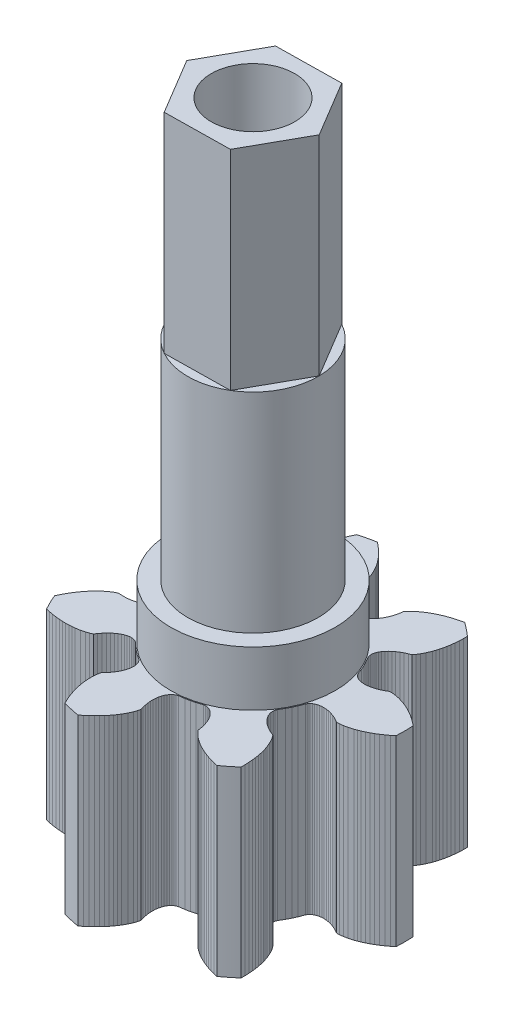
SolidWorks part; units mm, degrees
ref_plane "Front Plane" through (0, 0, 0) normal (0, 0, 1) x (1, 0, 0)
ref_plane "Top Plane" through (0, 0, 0) normal (0, 1, 0) x (1, 0, 0)
ref_plane "Right Plane" through (0, 0, 0) normal (1, 0, 0) x (0, 0, -1)
sketch "Sketch1" plane through (0, 0, 0) normal (0, 1, 0) x (1, 0, 0)
  circle A0 centre (0, 0) radius 3.15
  dimension "D1" = 6.3
extrude "Boss-Extrude1" add sketch "Sketch1" along normal blind 2.1
sketch "Sketch2" plane through (0, 2.1, 0) normal (0, 1, 0) x (1, 0, 0)
  circle A0 centre (0, 0) radius 2.5
  dimension "D1" = 5
extrude "Boss-Extrude3" add sketch "Sketch2" along normal blind 16
sketch "Sketch4" plane through (0, 0, 0) normal (0, -1, 0) x (1, 0, 0)
  line L420 (-1.6777, -5.4575) -> (-1.7402, -5.3144)
  line L421 (-1.7402, -5.3144) -> (-1.7939, -5.1757)
  line L422 (-1.7939, -5.1757) -> (-1.8392, -5.0423)
  line L423 (-1.8392, -5.0423) -> (-1.8764, -4.916)
  line L424 (-1.8764, -4.916) -> (-1.9071, -4.7932)
  line L425 (-1.9071, -4.7932) -> (-1.9311, -4.676)
  line L426 (-1.9311, -4.676) -> (-1.9488, -4.5668)
  line L427 (-1.9488, -4.5668) -> (-1.961, -4.464)
  line L428 (-1.961, -4.464) -> (-1.9715, -4.2798)
  line L429 (-1.9715, -4.2798) -> (-1.9674, -4.1246)
  line L430 (-1.9674, -4.1246) -> (-1.9537, -4.0009)
  line L431 (-1.9537, -4.0009) -> (-1.9303, -3.8867)
  line L432 (-1.9303, -3.8867) -> (-1.8594, -3.8097)
  line L433 (-1.8594, -3.8097) -> (-1.7784, -3.7125)
  line L434 (-1.7784, -3.7125) -> (-1.7087, -3.6155)
  line L435 (-1.7087, -3.6155) -> (-1.6501, -3.5195)
  line L436 (-1.6501, -3.5195) -> (-1.6023, -3.4251)
  line L437 (-1.6023, -3.4251) -> (-1.5652, -3.3333)
  line L438 (-1.5652, -3.3333) -> (-1.5384, -3.2446)
  line L439 (-1.5384, -3.2446) -> (-1.5215, -3.1597)
  line L440 (-1.5215, -3.1597) -> (-1.5143, -3.0795)
  line L441 (-1.5143, -3.0795) -> (-1.5162, -3.0043)
  line L442 (-1.5162, -3.0043) -> (-1.5269, -2.935)
  line L443 (-1.5269, -2.935) -> (-1.5457, -2.8721)
  line L444 (-1.5457, -2.8721) -> (-1.5723, -2.8162)
  line L445 (-1.5723, -2.8162) -> (-1.606, -2.7677)
  line L446 (-1.606, -2.7677) -> (-1.6572, -2.7183)
  line L447 (-1.6572, -2.7183) -> (-1.8447, -2.5928)
  line L448 (-1.8447, -2.5928) -> (-1.984, -2.4878)
  line L449 (-1.984, -2.4878) -> (-2.1173, -2.3754)
  line L450 (-2.1173, -2.3754) -> (-2.2814, -2.2205)
  line L451 (-2.2814, -2.2205) -> (-2.341, -2.1815)
  line L452 (-2.341, -2.1815) -> (-2.3957, -2.1595)
  line L453 (-2.3957, -2.1595) -> (-2.4562, -2.146)
  line L454 (-2.4562, -2.146) -> (-2.5217, -2.1417)
  line L455 (-2.5217, -2.1417) -> (-2.5917, -2.1467)
  line L456 (-2.5917, -2.1467) -> (-2.6653, -2.1615)
  line L457 (-2.6653, -2.1615) -> (-2.742, -2.1865)
  line L458 (-2.742, -2.1865) -> (-2.8209, -2.2218)
  line L459 (-2.8209, -2.2218) -> (-2.9014, -2.2676)
  line L460 (-2.9014, -2.2676) -> (-2.9827, -2.3243)
  line L461 (-2.9827, -2.3243) -> (-3.0641, -2.3918)
  line L462 (-3.0641, -2.3918) -> (-3.1447, -2.4703)
  line L463 (-3.1447, -2.4703) -> (-3.2237, -2.5599)
  line L464 (-3.2237, -2.5599) -> (-3.3005, -2.6605)
  line L465 (-3.3005, -2.6605) -> (-3.3598, -2.7467)
  line L466 (-3.3598, -2.7467) -> (-3.4659, -2.795)
  line L467 (-3.4659, -2.795) -> (-3.5835, -2.8358)
  line L468 (-3.5835, -2.8358) -> (-3.7338, -2.8744)
  line L469 (-3.7338, -2.8744) -> (-3.9158, -2.9052)
  line L470 (-3.9158, -2.9052) -> (-4.0187, -2.9161)
  line L471 (-4.0187, -2.9161) -> (-4.1291, -2.9232)
  line L472 (-4.1291, -2.9232) -> (-4.2487, -2.9258)
  line L473 (-4.2487, -2.9258) -> (-4.3752, -2.9233)
  line L474 (-4.3752, -2.9233) -> (-4.5067, -2.9151)
  line L475 (-4.5067, -2.9151) -> (-4.6468, -2.9006)
  line L476 (-4.6468, -2.9006) -> (-4.794, -2.8791)
  line L477 (-4.794, -2.8791) -> (-4.9474, -2.85)
  line L478 (-4.9474, -2.85) -> (-5.0902, -2.8167)
  line L479 (-5.3759, -2.2235) -> (-5.3129, -2.0911)
  line L480 (-5.3129, -2.0911) -> (-5.2399, -1.953)
  line L481 (-5.2399, -1.953) -> (-5.165, -1.8245)
  line L482 (-5.165, -1.8245) -> (-5.089, -1.7059)
  line L483 (-5.089, -1.7059) -> (-5.0134, -1.5981)
  line L484 (-5.0134, -1.5981) -> (-4.9365, -1.4976)
  line L485 (-4.9365, -1.4976) -> (-4.8599, -1.4057)
  line L486 (-4.8599, -1.4057) -> (-4.7855, -1.3238)
  line L487 (-4.7855, -1.3238) -> (-4.7128, -1.2502)
  line L488 (-4.7128, -1.2502) -> (-4.5753, -1.1271)
  line L489 (-4.5753, -1.1271) -> (-4.4514, -1.0336)
  line L490 (-4.4514, -1.0336) -> (-4.3462, -0.9671)
  line L491 (-4.3462, -0.9671) -> (-4.2422, -0.9142)
  line L492 (-4.2422, -0.9142) -> (-4.1379, -0.9217)
  line L493 (-4.1379, -0.9217) -> (-4.0114, -0.9244)
  line L494 (-4.0114, -0.9244) -> (-3.8921, -0.9184)
  line L495 (-3.8921, -0.9184) -> (-3.7804, -0.9043)
  line L496 (-3.7804, -0.9043) -> (-3.6769, -0.8828)
  line L497 (-3.6769, -0.8828) -> (-3.5819, -0.8546)
  line L498 (-3.5819, -0.8546) -> (-3.4959, -0.8203)
  line L499 (-3.4959, -0.8203) -> (-3.4191, -0.7805)
  line L500 (-3.4191, -0.7805) -> (-3.3518, -0.7361)
  line L501 (-3.3518, -0.7361) -> (-3.2942, -0.6878)
  line L502 (-3.2942, -0.6878) -> (-3.2467, -0.6363)
  line L503 (-3.2467, -0.6363) -> (-3.2093, -0.5823)
  line L504 (-3.2093, -0.5823) -> (-3.1821, -0.5267)
  line L505 (-3.1821, -0.5267) -> (-3.1652, -0.4701)
  line L506 (-3.1652, -0.4701) -> (-3.1585, -0.3992)
  line L507 (-3.1585, -0.3992) -> (-3.1773, -0.1744)
  line L508 (-3.1773, -0.1744) -> (-3.1821, 0)
  line L509 (-3.1821, 0) -> (-3.1773, 0.1743)
  line L510 (-3.1773, 0.1743) -> (-3.1585, 0.3991)
  line L511 (-3.1585, 0.3991) -> (-3.1652, 0.47)
  line L512 (-3.1652, 0.47) -> (-3.1821, 0.5266)
  line L513 (-3.1821, 0.5266) -> (-3.2093, 0.5822)
  line L514 (-3.2093, 0.5822) -> (-3.2467, 0.6362)
  line L515 (-3.2467, 0.6362) -> (-3.2942, 0.6877)
  line L516 (-3.2942, 0.6877) -> (-3.3518, 0.7361)
  line L517 (-3.3518, 0.7361) -> (-3.4191, 0.7805)
  line L518 (-3.4191, 0.7805) -> (-3.4959, 0.8202)
  line L519 (-3.4959, 0.8202) -> (-3.5819, 0.8545)
  line L520 (-3.5819, 0.8545) -> (-3.6769, 0.8828)
  line L521 (-3.6769, 0.8828) -> (-3.7804, 0.9043)
  line L522 (-3.7804, 0.9043) -> (-3.8921, 0.9183)
  line L523 (-3.8921, 0.9183) -> (-4.0114, 0.9243)
  line L524 (-4.0114, 0.9243) -> (-4.1379, 0.9216)
  line L525 (-4.1379, 0.9216) -> (-4.2422, 0.9142)
  line L526 (-4.2422, 0.9142) -> (-4.3462, 0.967)
  line L527 (-4.3462, 0.967) -> (-4.4514, 1.0335)
  line L528 (-4.4514, 1.0335) -> (-4.5753, 1.127)
  line L529 (-4.5753, 1.127) -> (-4.7128, 1.2501)
  line L530 (-4.7128, 1.2501) -> (-4.7855, 1.3238)
  line L531 (-4.7855, 1.3238) -> (-4.8599, 1.4056)
  line L532 (-4.8599, 1.4056) -> (-4.9365, 1.4975)
  line L533 (-4.9365, 1.4975) -> (-5.0134, 1.598)
  line L534 (-5.0134, 1.598) -> (-5.089, 1.7059)
  line L535 (-5.089, 1.7059) -> (-5.165, 1.8244)
  line L536 (-5.165, 1.8244) -> (-5.2399, 1.9529)
  line L537 (-5.2399, 1.9529) -> (-5.3129, 2.0911)
  line L538 (-5.3129, 2.0911) -> (-5.3759, 2.2234)
  line L539 (-5.0902, 2.8167) -> (-4.9474, 2.8499)
  line L540 (-4.9474, 2.8499) -> (-4.794, 2.879)
  line L541 (-4.794, 2.879) -> (-4.6468, 2.9005)
  line L542 (-4.6468, 2.9005) -> (-4.5067, 2.9151)
  line L543 (-4.5067, 2.9151) -> (-4.3752, 2.9232)
  line L544 (-4.3752, 2.9232) -> (-4.2487, 2.9257)
  line L545 (-4.2487, 2.9257) -> (-4.1291, 2.9231)
  line L546 (-4.1291, 2.9231) -> (-4.0187, 2.916)
  line L547 (-4.0187, 2.916) -> (-3.9158, 2.9051)
  line L548 (-3.9158, 2.9051) -> (-3.7338, 2.8743)
  line L549 (-3.7338, 2.8743) -> (-3.5835, 2.8358)
  line L550 (-3.5835, 2.8358) -> (-3.4659, 2.7949)
  line L551 (-3.4659, 2.7949) -> (-3.3598, 2.7466)
  line L552 (-3.3598, 2.7466) -> (-3.3005, 2.6604)
  line L553 (-3.3005, 2.6604) -> (-3.2237, 2.5598)
  line L554 (-3.2237, 2.5598) -> (-3.1447, 2.4703)
  line L555 (-3.1447, 2.4703) -> (-3.0641, 2.3918)
  line L556 (-3.0641, 2.3918) -> (-2.9827, 2.3242)
  line L557 (-2.9827, 2.3242) -> (-2.9014, 2.2676)
  line L558 (-2.9014, 2.2676) -> (-2.8209, 2.2217)
  line L559 (-2.8209, 2.2217) -> (-2.742, 2.1864)
  line L560 (-2.742, 2.1864) -> (-2.6653, 2.1615)
  line L561 (-2.6653, 2.1615) -> (-2.5917, 2.1466)
  line L562 (-2.5917, 2.1466) -> (-2.5217, 2.1416)
  line L563 (-2.5217, 2.1416) -> (-2.4562, 2.146)
  line L564 (-2.4562, 2.146) -> (-2.3957, 2.1594)
  line L565 (-2.3957, 2.1594) -> (-2.341, 2.1815)
  line L566 (-2.341, 2.1815) -> (-2.2814, 2.2205)
  line L567 (-2.2814, 2.2205) -> (-2.1173, 2.3753)
  line L568 (-2.1173, 2.3753) -> (-1.984, 2.4878)
  line L569 (-1.984, 2.4878) -> (-1.8447, 2.5927)
  line L570 (-1.8447, 2.5927) -> (-1.6572, 2.7182)
  line L571 (-1.6572, 2.7182) -> (-1.606, 2.7676)
  line L572 (-1.606, 2.7676) -> (-1.5723, 2.8161)
  line L573 (-1.5723, 2.8161) -> (-1.5457, 2.8721)
  line L574 (-1.5457, 2.8721) -> (-1.5269, 2.935)
  line L575 (-1.5269, 2.935) -> (-1.5162, 3.0043)
  line L576 (-1.5162, 3.0043) -> (-1.5143, 3.0794)
  line L577 (-1.5143, 3.0794) -> (-1.5215, 3.1597)
  line L578 (-1.5215, 3.1597) -> (-1.5384, 3.2445)
  line L579 (-1.5384, 3.2445) -> (-1.5652, 3.3332)
  line L580 (-1.5652, 3.3332) -> (-1.6023, 3.4251)
  line L581 (-1.6023, 3.4251) -> (-1.6501, 3.5194)
  line L582 (-1.6501, 3.5194) -> (-1.7087, 3.6154)
  line L583 (-1.7087, 3.6154) -> (-1.7784, 3.7125)
  line L584 (-1.7784, 3.7125) -> (-1.8594, 3.8097)
  line L585 (-1.8594, 3.8097) -> (-1.9303, 3.8866)
  line L586 (-1.9303, 3.8866) -> (-1.9537, 4.0009)
  line L587 (-1.9537, 4.0009) -> (-1.9674, 4.1246)
  line L588 (-1.9674, 4.1246) -> (-1.9715, 4.2797)
  line L589 (-1.9715, 4.2797) -> (-1.961, 4.464)
  line L590 (-1.961, 4.464) -> (-1.9488, 4.5668)
  line L591 (-1.9488, 4.5668) -> (-1.9311, 4.6759)
  line L592 (-1.9311, 4.6759) -> (-1.9071, 4.7932)
  line L593 (-1.9071, 4.7932) -> (-1.8764, 4.9159)
  line L594 (-1.8764, 4.9159) -> (-1.8392, 5.0423)
  line L595 (-1.8392, 5.0423) -> (-1.7939, 5.1756)
  line L596 (-1.7939, 5.1756) -> (-1.7402, 5.3143)
  line L597 (-1.7402, 5.3143) -> (-1.6777, 5.4575)
  line L598 (-1.6777, 5.4575) -> (-1.6135, 5.5893)
  line L599 (-0.9715, 5.7358) -> (-0.8565, 5.6449)
  line L600 (-0.8565, 5.6449) -> (-0.7381, 5.543)
  line L601 (-0.7381, 5.543) -> (-0.6295, 5.4414)
  line L602 (-0.6295, 5.4414) -> (-0.5308, 5.3409)
  line L603 (-0.5308, 5.3409) -> (-0.4425, 5.2432)
  line L604 (-0.4425, 5.2432) -> (-0.3616, 5.1459)
  line L605 (-0.3616, 5.1459) -> (-0.2891, 5.0507)
  line L606 (-0.2891, 5.0507) -> (-0.2258, 4.96)
  line L607 (-0.2258, 4.96) -> (-0.1702, 4.8727)
  line L608 (-0.1702, 4.8727) -> (-0.0808, 4.7113)
  line L609 (-0.0808, 4.7113) -> (-0.0172, 4.5697)
  line L610 (-0.0172, 4.5697) -> (0.0242, 4.4523)
  line L611 (0.0242, 4.4523) -> (0.0526, 4.3392)
  line L612 (0.0526, 4.3392) -> (0.0222, 4.2391)
  line L613 (0.0222, 4.2391) -> (-0.0086, 4.1164)
  line L614 (-0.0086, 4.1164) -> (-0.0293, 3.9987)
  line L615 (-0.0293, 3.9987) -> (-0.0405, 3.8868)
  line L616 (-0.0405, 3.8868) -> (-0.0426, 3.7811)
  line L617 (-0.0426, 3.7811) -> (-0.0362, 3.6822)
  line L618 (-0.0362, 3.6822) -> (-0.0218, 3.5907)
  line L619 (-0.0218, 3.5907) -> (-0.0002, 3.5069)
  line L620 (-0.0002, 3.5069) -> (0.0281, 3.4314)
  line L621 (0.0281, 3.4314) -> (0.0624, 3.3646)
  line L622 (0.0624, 3.3646) -> (0.1021, 3.3068)
  line L623 (0.1021, 3.3068) -> (0.1464, 3.2583)
  line L624 (0.1464, 3.2583) -> (0.1946, 3.2194)
  line L625 (0.1946, 3.2194) -> (0.246, 3.1903)
  line L626 (0.246, 3.1903) -> (0.3136, 3.1681)
  line L627 (0.3136, 3.1681) -> (0.537, 3.1363)
  line L628 (0.537, 3.1363) -> (0.708, 3.1022)
  line L629 (0.708, 3.1022) -> (0.8769, 3.0588)
  line L630 (0.8769, 3.0588) -> (1.0919, 2.9904)
  line L631 (1.0919, 2.9904) -> (1.1625, 2.9811)
  line L632 (1.1625, 2.9811) -> (1.2214, 2.985)
  line L633 (1.2214, 2.985) -> (1.2817, 2.9991)
  line L634 (1.2817, 2.9991) -> (1.3427, 3.0236)
  line L635 (1.3427, 3.0236) -> (1.4035, 3.0585)
  line L636 (1.4035, 3.0585) -> (1.4634, 3.1038)
  line L637 (1.4634, 3.1038) -> (1.5217, 3.1596)
  line L638 (1.5217, 3.1596) -> (1.5775, 3.2256)
  line L639 (1.5775, 3.2256) -> (1.6301, 3.3019)
  line L640 (1.6301, 3.3019) -> (1.6788, 3.3882)
  line L641 (1.6788, 3.3882) -> (1.7228, 3.4843)
  line L642 (1.7228, 3.4843) -> (1.7613, 3.59)
  line L643 (1.7613, 3.59) -> (1.7937, 3.705)
  line L644 (1.7937, 3.705) -> (1.8192, 3.829)
  line L645 (1.8192, 3.829) -> (1.8352, 3.9324)
  line L646 (1.8352, 3.9324) -> (1.9099, 4.0219)
  line L647 (1.9099, 4.0219) -> (1.9981, 4.1097)
  line L648 (1.9981, 4.1097) -> (2.1168, 4.2097)
  line L649 (2.1168, 4.2097) -> (2.2674, 4.3164)
  line L650 (2.2674, 4.3164) -> (2.3554, 4.3709)
  line L651 (2.3554, 4.3709) -> (2.4518, 4.4251)
  line L652 (2.4518, 4.4251) -> (2.5584, 4.4794)
  line L653 (2.5584, 4.4794) -> (2.6735, 4.532)
  line L654 (2.6735, 4.532) -> (2.7955, 4.5817)
  line L655 (2.7955, 4.5817) -> (2.928, 4.6294)
  line L656 (2.928, 4.6294) -> (3.0699, 4.6739)
  line L657 (3.0699, 4.6739) -> (3.2208, 4.7143)
  line L658 (3.2208, 4.7143) -> (3.3639, 4.7463)
  line L659 (3.8787, 4.3357) -> (3.8793, 4.1891)
  line L660 (3.8793, 4.1891) -> (3.8735, 4.033)
  line L661 (3.8735, 4.033) -> (3.8618, 3.8847)
  line L662 (3.8618, 3.8847) -> (3.8448, 3.7449)
  line L663 (3.8448, 3.7449) -> (3.8234, 3.615)
  line L664 (3.8234, 3.615) -> (3.7978, 3.4911)
  line L665 (3.7978, 3.4911) -> (3.7686, 3.375)
  line L666 (3.7686, 3.375) -> (3.7371, 3.269)
  line L667 (3.7371, 3.269) -> (3.7036, 3.1711)
  line L668 (3.7036, 3.1711) -> (3.6331, 3.0005)
  line L669 (3.6331, 3.0005) -> (3.562, 2.8625)
  line L670 (3.562, 2.8625) -> (3.4961, 2.757)
  line L671 (3.4961, 2.757) -> (3.4253, 2.6643)
  line L672 (3.4253, 2.6643) -> (3.3281, 2.6257)
  line L673 (3.3281, 2.6257) -> (3.213, 2.5732)
  line L674 (3.213, 2.5732) -> (3.1081, 2.516)
  line L675 (3.1081, 2.516) -> (3.0136, 2.4549)
  line L676 (3.0136, 2.4549) -> (2.9296, 2.3907)
  line L677 (2.9296, 2.3907) -> (2.8563, 2.324)
  line L678 (2.8563, 2.324) -> (2.7937, 2.2557)
  line L679 (2.7937, 2.2557) -> (2.7417, 2.1866)
  line L680 (2.7417, 2.1866) -> (2.7003, 2.1174)
  line L681 (2.7003, 2.1174) -> (2.6695, 2.0489)
  line L682 (2.6695, 2.0489) -> (2.649, 1.9819)
  line L683 (2.649, 1.9819) -> (2.6387, 1.917)
  line L684 (2.6387, 1.917) -> (2.6383, 1.8551)
  line L685 (2.6383, 1.8551) -> (2.6476, 1.7967)
  line L686 (2.6476, 1.7967) -> (2.6724, 1.73)
  line L687 (2.6724, 1.73) -> (2.7869, 1.5356)
  line L688 (2.7869, 1.5356) -> (2.8668, 1.3806)
  line L689 (2.8668, 1.3806) -> (2.9382, 1.2215)
  line L690 (2.9382, 1.2215) -> (3.0188, 1.0107)
  line L691 (3.0188, 1.0107) -> (3.0555, 0.9498)
  line L692 (3.0555, 0.9498) -> (3.0953, 0.9061)
  line L693 (3.0953, 0.9061) -> (3.144, 0.8678)
  line L694 (3.144, 0.8678) -> (3.2011, 0.8354)
  line L695 (3.2011, 0.8354) -> (3.2663, 0.8096)
  line L696 (3.2663, 0.8096) -> (3.3391, 0.791)
  line L697 (3.3391, 0.791) -> (3.419, 0.7802)
  line L698 (3.419, 0.7802) -> (3.5054, 0.7777)
  line L699 (3.5054, 0.7777) -> (3.5979, 0.7842)
  line L700 (3.5979, 0.7842) -> (3.6957, 0.7999)
  line L701 (3.6957, 0.7999) -> (3.7983, 0.8255)
  line L702 (3.7983, 0.8255) -> (3.905, 0.8612)
  line L703 (3.905, 0.8612) -> (4.0151, 0.9076)
  line L704 (4.0151, 0.9076) -> (4.1279, 0.9649)
  line L705 (4.1279, 0.9649) -> (4.2187, 1.0169)
  line L706 (4.2187, 1.0169) -> (4.3353, 1.0144)
  line L707 (4.3353, 1.0144) -> (4.4589, 1.0001)
  line L708 (4.4589, 1.0001) -> (4.6111, 0.9696)
  line L709 (4.6111, 0.9696) -> (4.7884, 0.9184)
  line L710 (4.7884, 0.9184) -> (4.8859, 0.8836)
  line L711 (4.8859, 0.8836) -> (4.9884, 0.8421)
  line L712 (4.9884, 0.8421) -> (5.0973, 0.7926)
  line L713 (5.0973, 0.7926) -> (5.2102, 0.7354)
  line L714 (5.2102, 0.7354) -> (5.3251, 0.671)
  line L715 (5.3251, 0.671) -> (5.445, 0.5972)
  line L716 (5.445, 0.5972) -> (5.5683, 0.5139)
  line L717 (5.5683, 0.5139) -> (5.6939, 0.4211)
  line L718 (5.6939, 0.4211) -> (5.8081, 0.3292)
  line L719 (5.8081, -0.3293) -> (5.6939, -0.4212)
  line L720 (5.6939, -0.4212) -> (5.5683, -0.514)
  line L721 (5.5683, -0.514) -> (5.445, -0.5972)
  line L722 (5.445, -0.5972) -> (5.3251, -0.6711)
  line L723 (5.3251, -0.6711) -> (5.2102, -0.7354)
  line L724 (5.2102, -0.7354) -> (5.0973, -0.7926)
  line L725 (5.0973, -0.7926) -> (4.9884, -0.8421)
  line L726 (4.9884, -0.8421) -> (4.8859, -0.8837)
  line L727 (4.8859, -0.8837) -> (4.7884, -0.9185)
  line L728 (4.7884, -0.9185) -> (4.6111, -0.9697)
  line L729 (4.6111, -0.9697) -> (4.4589, -1.0002)
  line L730 (4.4589, -1.0002) -> (4.3353, -1.0144)
  line L731 (4.3353, -1.0144) -> (4.2187, -1.017)
  line L732 (4.2187, -1.017) -> (4.1279, -0.965)
  line L733 (4.1279, -0.965) -> (4.0151, -0.9077)
  line L734 (4.0151, -0.9077) -> (3.905, -0.8613)
  line L735 (3.905, -0.8613) -> (3.7983, -0.8255)
  line L736 (3.7983, -0.8255) -> (3.6957, -0.8)
  line L737 (3.6957, -0.8) -> (3.5979, -0.7842)
  line L738 (3.5979, -0.7842) -> (3.5054, -0.7778)
  line L739 (3.5054, -0.7778) -> (3.419, -0.7803)
  line L740 (3.419, -0.7803) -> (3.3391, -0.7911)
  line L741 (3.3391, -0.7911) -> (3.2663, -0.8097)
  line L742 (3.2663, -0.8097) -> (3.2011, -0.8354)
  line L743 (3.2011, -0.8354) -> (3.144, -0.8678)
  line L744 (3.144, -0.8678) -> (3.0953, -0.9062)
  line L745 (3.0953, -0.9062) -> (3.0555, -0.9498)
  line L746 (3.0555, -0.9498) -> (3.0188, -1.0108)
  line L747 (3.0188, -1.0108) -> (2.9382, -1.2215)
  line L748 (2.9382, -1.2215) -> (2.8668, -1.3806)
  line L749 (2.8668, -1.3806) -> (2.7869, -1.5356)
  line L750 (2.7869, -1.5356) -> (2.6724, -1.7301)
  line L751 (2.6724, -1.7301) -> (2.6476, -1.7968)
  line L752 (2.6476, -1.7968) -> (2.6383, -1.8551)
  line L753 (2.6383, -1.8551) -> (2.6387, -1.9171)
  line L754 (2.6387, -1.9171) -> (2.649, -1.9819)
  line L755 (2.649, -1.9819) -> (2.6695, -2.049)
  line L756 (2.6695, -2.049) -> (2.7003, -2.1175)
  line L757 (2.7003, -2.1175) -> (2.7417, -2.1867)
  line L758 (2.7417, -2.1867) -> (2.7937, -2.2558)
  line L759 (2.7937, -2.2558) -> (2.8563, -2.3241)
  line L760 (2.8563, -2.3241) -> (2.9296, -2.3907)
  line L761 (2.9296, -2.3907) -> (3.0136, -2.455)
  line L762 (3.0136, -2.455) -> (3.1081, -2.5161)
  line L763 (3.1081, -2.5161) -> (3.213, -2.5733)
  line L764 (3.213, -2.5733) -> (3.3281, -2.6257)
  line L765 (3.3281, -2.6257) -> (3.4253, -2.6643)
  line L766 (3.4253, -2.6643) -> (3.4961, -2.757)
  line L767 (3.4961, -2.757) -> (3.562, -2.8626)
  line L768 (3.562, -2.8626) -> (3.6331, -3.0006)
  line L769 (3.6331, -3.0006) -> (3.7036, -3.1711)
  line L770 (3.7036, -3.1711) -> (3.7371, -3.2691)
  line L771 (3.7371, -3.2691) -> (3.7686, -3.3751)
  line L772 (3.7686, -3.3751) -> (3.7978, -3.4911)
  line L773 (3.7978, -3.4911) -> (3.8234, -3.615)
  line L774 (3.8234, -3.615) -> (3.8448, -3.745)
  line L775 (3.8448, -3.745) -> (3.8618, -3.8848)
  line L776 (3.8618, -3.8848) -> (3.8735, -4.0331)
  line L777 (3.8735, -4.0331) -> (3.8793, -4.1892)
  line L778 (3.8793, -4.1892) -> (3.8787, -4.3358)
  line L779 (3.3639, -4.7463) -> (3.2208, -4.7143)
  line L780 (3.2208, -4.7143) -> (3.0699, -4.6739)
  line L781 (3.0699, -4.6739) -> (2.928, -4.6295)
  line L782 (2.928, -4.6295) -> (2.7955, -4.5818)
  line L783 (2.7955, -4.5818) -> (2.6735, -4.5321)
  line L784 (2.6735, -4.5321) -> (2.5584, -4.4795)
  line L785 (2.5584, -4.4795) -> (2.4518, -4.4252)
  line L786 (2.4518, -4.4252) -> (2.3554, -4.3709)
  line L787 (2.3554, -4.3709) -> (2.2674, -4.3164)
  line L788 (2.2674, -4.3164) -> (2.1168, -4.2097)
  line L789 (2.1168, -4.2097) -> (1.9981, -4.1098)
  line L790 (1.9981, -4.1098) -> (1.9099, -4.022)
  line L791 (1.9099, -4.022) -> (1.8352, -3.9324)
  line L792 (1.8352, -3.9324) -> (1.8192, -3.829)
  line L793 (1.8192, -3.829) -> (1.7937, -3.7051)
  line L794 (1.7937, -3.7051) -> (1.7613, -3.5901)
  line L795 (1.7613, -3.5901) -> (1.7228, -3.4844)
  line L796 (1.7228, -3.4844) -> (1.6788, -3.3883)
  line L797 (1.6788, -3.3883) -> (1.6301, -3.3019)
  line L798 (1.6301, -3.3019) -> (1.5775, -3.2257)
  line L799 (1.5775, -3.2257) -> (1.5217, -3.1596)
  line L800 (1.5217, -3.1596) -> (1.4634, -3.1039)
  line L801 (1.4634, -3.1039) -> (1.4035, -3.0586)
  line L802 (1.4035, -3.0586) -> (1.3427, -3.0237)
  line L803 (1.3427, -3.0237) -> (1.2817, -2.9992)
  line L804 (1.2817, -2.9992) -> (1.2214, -2.9851)
  line L805 (1.2214, -2.9851) -> (1.1625, -2.9812)
  line L806 (1.1625, -2.9812) -> (1.0919, -2.9905)
  line L807 (1.0919, -2.9905) -> (0.8769, -3.0588)
  line L808 (0.8769, -3.0588) -> (0.708, -3.1023)
  line L809 (0.708, -3.1023) -> (0.537, -3.1364)
  line L810 (0.537, -3.1364) -> (0.3136, -3.1681)
  line L811 (0.3136, -3.1681) -> (0.246, -3.1904)
  line L812 (0.246, -3.1904) -> (0.1946, -3.2194)
  line L813 (0.1946, -3.2194) -> (0.1464, -3.2583)
  line L814 (0.1464, -3.2583) -> (0.1021, -3.3068)
  line L815 (0.1021, -3.3068) -> (0.0624, -3.3647)
  line L816 (0.0624, -3.3647) -> (0.0281, -3.4315)
  line L817 (0.0281, -3.4315) -> (-0.0002, -3.507)
  line L818 (-0.0002, -3.507) -> (-0.0218, -3.5907)
  line L819 (-0.0218, -3.5907) -> (-0.0362, -3.6823)
  line L820 (-0.0362, -3.6823) -> (-0.0426, -3.7811)
  line L821 (-0.0426, -3.7811) -> (-0.0405, -3.8868)
  line L822 (-0.0405, -3.8868) -> (-0.0293, -3.9988)
  line L823 (-0.0293, -3.9988) -> (-0.0086, -4.1165)
  line L824 (-0.0086, -4.1165) -> (0.0222, -4.2392)
  line L825 (0.0222, -4.2392) -> (0.0526, -4.3393)
  line L826 (0.0526, -4.3393) -> (0.0242, -4.4524)
  line L827 (0.0242, -4.4524) -> (-0.0172, -4.5698)
  line L828 (-0.0172, -4.5698) -> (-0.0808, -4.7113)
  line L829 (-0.0808, -4.7113) -> (-0.1702, -4.8728)
  line L830 (-0.1702, -4.8728) -> (-0.2258, -4.9601)
  line L831 (-0.2258, -4.9601) -> (-0.2891, -5.0508)
  line L832 (-0.2891, -5.0508) -> (-0.3616, -5.146)
  line L833 (-0.3616, -5.146) -> (-0.4425, -5.2433)
  line L834 (-0.4425, -5.2433) -> (-0.5308, -5.341)
  line L835 (-0.5308, -5.341) -> (-0.6295, -5.4414)
  line L836 (-0.6295, -5.4414) -> (-0.7381, -5.5431)
  line L837 (-0.7381, -5.5431) -> (-0.8565, -5.645)
  line L838 (-0.8565, -5.645) -> (-0.9715, -5.7359)
  line L839 (-1.6135, -5.5894) -> (-1.6777, -5.4575)
  arc A7 (-5.3759, -2.2235) -> (-5.0902, -2.8167) centre (0, 0) ccw
  arc A8 (-5.0902, 2.8167) -> (-5.3759, 2.2234) centre (0, -0.0001) ccw
  arc A9 (-0.9715, 5.7358) -> (-1.6135, 5.5893) centre (0, -0.0001) ccw
  arc A10 (3.8787, 4.3357) -> (3.3639, 4.7463) centre (-0.0001, -0.0001) ccw
  arc A11 (5.8081, -0.3293) -> (5.8081, 0.3292) centre (-0.0001, 0) ccw
  arc A12 (3.3639, -4.7463) -> (3.8787, -4.3358) centre (-0.0001, 0) ccw
  arc A13 (-1.6135, -5.5894) -> (-0.9715, -5.7359) centre (0, 0) ccw
extrude "Boss-Extrude4" add sketch "Sketch4" along normal blind 7
sketch "Sketch3" plane through (0, 0, 0) normal (0, -1, 0) x (1, 0, 0)
  circle A0 centre (0, 0) radius 1.1
  circle A1 centre (0, 0) radius 0.75
  dimension "D1" = 2.2
  dimension "D2" = 1.5
extrude "Cut-Extrude2" cut sketch "Sketch3" along normal through all contours A0 A1 | A1 region at (-1.0689, 0, 0) region at (0, 0, 0)
ref_plane "Plane2" through (0, 5.9, 0) normal (0, 1, 0) x (1, 0, 0)
sketch "Sketch6" plane through (0, -7, 0) normal (0, -1, 0) x (1, 0, 0)
  circle A0 centre (0, 0) radius 1.7
  dimension "D1" = 3.4
extrude "Cut-Extrude3" cut sketch "Sketch6" against normal offset from surface (7.6 mm away) 1.5 up to face at (0, 2.1, 2.5)
sketch "Sketch7" plane through (0, 0.6, 0) normal (0, -1, 0) x (1, 0, 0)
  circle A0 centre (0, 0) radius 1.6
  dimension "D1" = 3.2
ref_plane "Plane4" through (0, 8.1, 0) normal (0, 1, 0) x (1, 0, 0)
extrude "Cut-Extrude4" cut sketch "Sketch7" against normal through all
sketch "Sketch8" plane through (0, 18.1, 0) normal (0, 1, 0) x (1, 0, 0)
  line L6 (1.2824, -2.1461) -> (2.4997, 0.0375)
  line L7 (2.4997, 0.0375) -> (1.2174, 2.1836)
  line L8 (1.2174, 2.1836) -> (-1.2824, 2.1461)
  line L9 (-1.2824, 2.1461) -> (-2.4997, -0.0375)
  line L10 (-2.4997, -0.0375) -> (-1.2174, -2.1836)
  line L11 (-1.2174, -2.1836) -> (1.2824, -2.1461)
  circle A3 centre (0, 0) radius 2.5 construction
  circle A4 centre (0, 0) radius 2.5 construction
extrude "Cut-Extrude5" cut sketch "Sketch8" against normal blind 8 flip side to cut contours L8 L9 L10 L11 L6 L7
